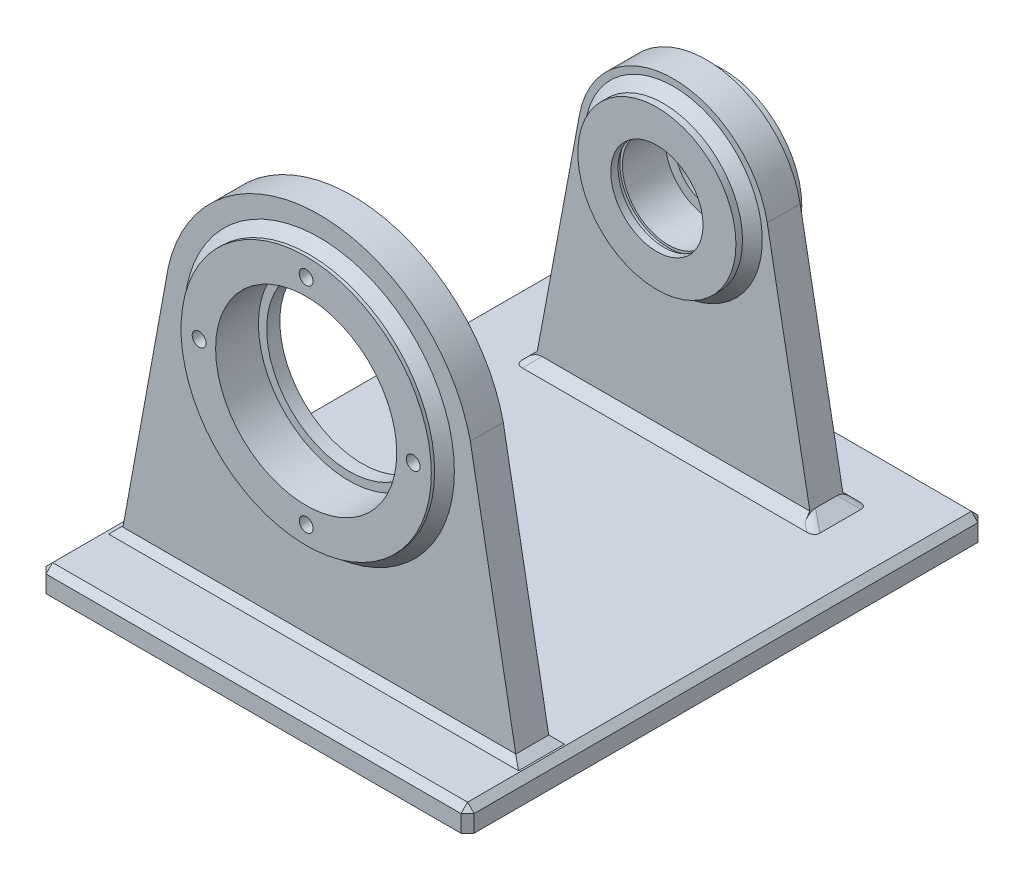
SolidWorks part; units mm, degrees
ref_plane "Front Plane" through (0, 0, 0) normal (0, 0, 1) x (1, 0, 0)
ref_plane "Top Plane" through (0, 0, 0) normal (0, 1, 0) x (1, 0, 0)
ref_plane "Right Plane" through (0, 0, 0) normal (1, 0, 0) x (0, 0, -1)
sketch "Sketch1" plane through (0, 0, 0) normal (0, 0, 1) x (1, 0, 0)
  line L0 (0, 0) -> (0, -96.4925) construction
  line L2 (-65, -67) -> (65, -67)
  line L3 (-65, -67) -> (-65, -74.1841)
  line L4 (-65, -74.1841) -> (65, -74.1841)
  line L5 (65, -67) -> (65, -74.1841)
  dimension "D1" = 65
  dimension "D2" = 130
  dimension "D3" = 67
  dimension "D4" = 7.1841
extrude "Extrude2" add sketch "Sketch1" against normal blind 157
ref_plane "Plane1" through (0, 0, -20) normal (0, 0, 1) x (1, 0, 0)
sketch "Sketch2" plane through (0, 0, -20) normal (0, 0, 1) x (1, 0, 0)
  line L2 (-60, -67) -> (-45.8644, 10.2692)
  line L3 (45.8561, 10.306) -> (60, -67)
  line L5 (-65, -67) -> (-65, -74.1841) construction
  line L6 (65, -74.1841) -> (65, -67) construction
  line L7 (65, -67) -> (-65, -67) construction
  line L8 (-60, -67) -> (60, -67)
  arc A0 (-45.8644, 10.2692) -> (45.8561, 10.306) centre (0, 0) cw
  dimension "D1" = 5
  dimension "D5" = 47
  dimension "D2" = 5
  dimension "D3" = 65
  dimension "D4" = 67
  dimension "D6" = 79.633
  dimension "D7" = 79.632
  dimension "D8" = 77.2692
  dimension "D9" = 77.306
extrude "Extrude3" add sketch "Sketch2" against normal blind 10
sketch "Sketch3" plane through (0, 0, -20) normal (0, 0, 1) x (1, 0, 0)
  circle A0 centre (0, 0) radius 38
  dimension "D1" = 76
extrude "Extrude4" add sketch "Sketch3" along normal blind 4 and the other way blind 13
sketch "Sketch4" plane through (0, 0, -16) normal (0, 0, 1) x (1, 0, 0)
  circle A0 centre (0, 0) radius 25
  dimension "D1" = 50
extrude "Cut-Extrude1" cut sketch "Sketch4" against normal through all
sketch "Sketch5" plane through (0, 0, -16) normal (0, 0, 1) x (1, 0, 0)
  circle A0 centre (0, 0) radius 27.5
  dimension "D1" = 55
extrude "Cut-Extrude2" cut sketch "Sketch5" against normal blind 13
hole_wizard "M5 Tapped Hole1" positions "Sketch9" profile "Sketch8" tap size "M5" standard "GB"
sketch "Sketch9" plane through (0, 0, -16) normal (0, 0, 1) x (1, 0, 0)
  line L0 (0, 0) -> (-0.0189, 47) construction
  arc A0 (45.8561, 10.306) -> (-45.8644, 10.2692) centre (0, 0) ccw construction
  point P0 (-0.013, 32.5)
  dimension "D1" = 32.5
sketch "Sketch8" plane through (-0.013, 32.5, -16) normal (1, 0, 0) x (0, -1, 0)
  line L0 (0, 0) -> (0, 15.6618)
  line L1 (0, 15.6618) -> (2.1, 14.4)
  line L2 (2.1, 14.4) -> (2.1, 0)
  line L5 (2.1, 0) -> (0, 0)
  line L10 (0, 15.6618) -> (-2.1, 14.4) construction
  line L11 (0, -6.35) -> (0, 107.95) construction
  dimension "Tap Drill Dia." = 4.2
  dimension "Tap Drill Depth" = 14.4
  dimension "Drill Angle" = 118
cosmetic thread "Hole Thread1" parameters "D1"=10, "D2"=5
pattern_circular "CirPattern1" count 4 over 360 about axis through (0, 0, 0) along (0, 0, 1) of "M5 Tapped Hole1"
ref_plane "Plane2" through (0, 0, -127.5) normal (0, 0, 1) x (1, 0, 0)
sketch "Sketch10" plane through (0, 0, -127.5) normal (0, 0, 1) x (1, 0, 0)
  line L0 (-42, -67) -> (-28.5081, 5.3185)
  line L1 (-42, -67) -> (42, -67)
  line L4 (28.5081, 5.3185) -> (42, -67)
  line L5 (65, -74.1841) -> (65, -67) construction
  line L6 (-65, -67) -> (-65, -74.1841) construction
  arc A0 (-28.5081, 5.3185) -> (28.5081, 5.3185) centre (0, 0) cw
  dimension "D1" = 29
  dimension "D2" = 67
  dimension "D4" = 23
  dimension "D5" = 23
extrude "Extrude6" add sketch "Sketch10" against normal blind 10
sketch "Sketch11" plane through (0, 0, -127.5) normal (0, 0, 1) x (1, 0, 0)
  circle A0 centre (0, 0) radius 24
  dimension "D2" = 48
extrude "Extrude7" add sketch "Sketch11" along normal blind 5 and the other way blind 15
sketch "Sketch12" plane through (0, 0, -122.5) normal (0, 0, 1) x (1, 0, 0)
  circle A0 centre (0, 0) radius 14
  dimension "D1" = 28
extrude "Cut-Extrude3" cut sketch "Sketch12" against normal blind 35
chamfer "Chamfer1" distance 3 angle 45 1 edges at (-38, 0, -20)
chamfer "Chamfer2" distance 3 angle 45 1 edges at (-38, 0, -30)
chamfer "Chamfer3" distance 2 angle 45 4 edges at (-60, -67, -25) (60, -67, -25) (0, -67, -20) (0, -67, -30)
chamfer "Chamfer4" distance 3 angle 45 1 edges at (-24, 0, -127.5)
ref_plane "Plane3" through (0, 0, -126) normal (0, 0, 1) x (1, 0, 0)
sketch "Sketch13" plane through (0, 0, -126) normal (0, 0, 1) x (1, 0, 0)
  circle A0 centre (0, 0) radius 14.75
  dimension "D1" = 29.5
extrude "Cut-Extrude4" cut sketch "Sketch13" along normal blind 1.3
ref_plane "Plane4" through (0, 0, -139) normal (0, 0, 1) x (1, 0, 0)
fillet "Fillet3" radius 3 4 edges at (-43.5, -65.5, -126) (-43.5, -65.5, -139) (43.6007, -65.5254, -139.0254) (43.6007, -65.5254, -125.9746)
sketch "Sketch14" plane through (0, 0, -139) normal (0, 0, 1) x (1, 0, 0)
  circle A0 centre (0, 0) radius 11
  circle A1 centre (0, 0) radius 17.5
  dimension "D1" = 22
  dimension "D2" = 35
extrude "Extrude8" add sketch "Sketch14" against normal up to surface (3.5 mm away) up to face at (14, 0, -142.5)
hole_wizard "M5 Tapped Hole2" positions "Sketch16" profile "Sketch15" tap size "M5" standard "GB"
sketch "Sketch16" plane through (0, 0, -142.5) normal (0, 0, -1) x (-1, 0, 0)
  line L0 (0, 0) -> (0, 24) construction
  circle A0 centre (0, 0) radius 24 construction
  point P0 (0, 18)
  dimension "D1" = 18
sketch "Sketch15" plane through (0, 18, -142.5) normal (1, 0, 0) x (0, 1, 0)
  line L0 (0, 0) -> (0, 16.2618)
  line L1 (0, 16.2618) -> (2.1, 15)
  line L2 (2.1, 15) -> (2.1, 0)
  line L5 (2.1, 0) -> (0, 0)
  line L10 (0, 16.2618) -> (-2.1, 15) construction
  line L11 (0, -6.35) -> (0, 107.95) construction
  dimension "Tap Drill Dia." = 4.2
  dimension "Tap Drill Depth" = 15
  dimension "Drill Angle" = 118
cosmetic thread "Hole Thread2" parameters "D1"=12, "D2"=5
pattern_circular "CirPattern2" count 4 over 360 about axis through (0, 0, 0) along (0, 0, 1) of "M5 Tapped Hole2"
chamfer "Chamfer8" distance 2 angle 45 8 edges at (65, -67, -78.5) (65, -70.592, -157) (-65, -70.592, -157) (-65, -70.592, 0) (65, -70.592, 0) (0, -67, -157) (-65, -67, -78.5) (0, -67, 0)
